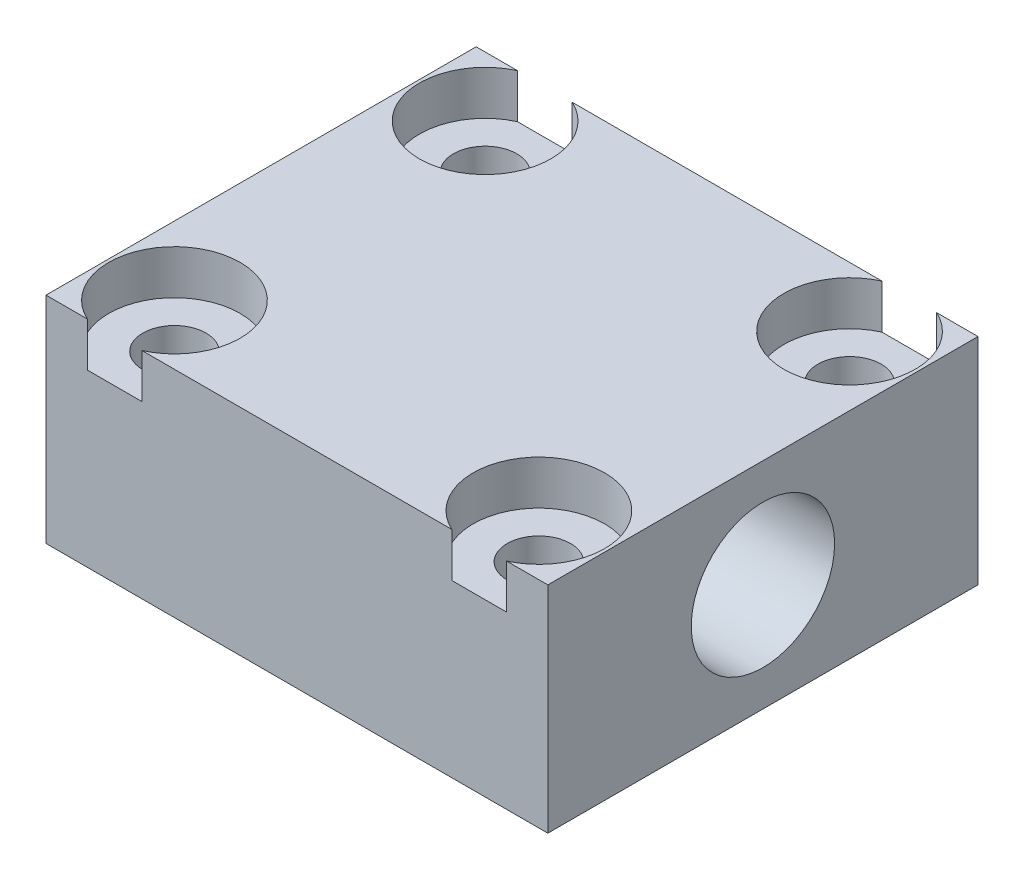
SolidWorks part; units mm, degrees
ref_plane "Front Plane" through (0, 0, 0) normal (0, 0, 1) x (1, 0, 0)
ref_plane "Top Plane" through (0, 0, 0) normal (0, 1, 0) x (1, 0, 0)
ref_plane "Right Plane" through (0, 0, 0) normal (1, 0, 0) x (0, 0, -1)
sketch "Sketch1" plane through (0, 0, 0) normal (0, 1, 0) x (1, 0, 0)
  line L1 (-21, 18) -> (21, 18)
  line L2 (-21, 18) -> (-21, -18)
  line L3 (-21, -18) -> (21, -18)
  line L4 (21, 18) -> (21, -18)
  line L5 (-21, 18) -> (21, -18) construction
  line L6 (-21, -18) -> (21, 18) construction
  point P0 (0, 0)
  dimension "D1" = 36
  dimension "D2" = 42
extrude "Boss-Extrude1" add sketch "Sketch1" along normal blind 18
sketch "Sketch4" plane through (0, 0, 0) normal (0, -1, 0) x (1, 0, 0)
  line L1 (-15.25, -13) -> (15.25, -13) construction
  line L2 (-15.25, -13) -> (-15.25, 13) construction
  line L3 (-15.25, 13) -> (15.25, 13) construction
  line L4 (15.25, -13) -> (15.25, 13) construction
  line L5 (-15.25, -13) -> (15.25, 13) construction
  line L6 (-15.25, 13) -> (15.25, -13) construction
  point P0 (0, 0)
  dimension "D1" = 30.5
  dimension "D2" = 26
hole_wizard "CBORE for M5 Pan Head Machine Screw3" positions "Sketch6" profile "Sketch5" counterbore size "M5" standard "ANSI Metric" end condition through all
sketch "Sketch6" plane through (-6.5491, 18, -3.6896) normal (0, -1, 0) x (-1, 0, 0)
  point P0 (8.7009, -16.6896)
  point P3 (-21.7991, -16.6896)
  point P6 (-21.7991, 9.3104)
  point P9 (8.7009, 9.3104)
sketch "Sketch5" plane through (-15.25, 18, 13) normal (1, 0, 0) x (0, 0, 1)
  line L0 (0, 0) -> (0, 18)
  line L1 (0, 18) -> (2.65, 18)
  line L3 (2.65, 18) -> (2.65, 3.7)
  line L4 (2.65, 3.7) -> (5.5, 3.7)
  line L5 (5.5, 3.7) -> (5.5, 0)
  line L7 (5.5, 0) -> (0, 0)
  line L11 (0, -6.35) -> (0, 107.95) construction
  dimension "Thru Hole Dia." = 5.3
  dimension "Thru Hole Depth" = 18
  dimension "C'Bore Dia." = 11
  dimension "C'Bore Depth" = 3.7
sketch "Sketch7" plane through (21, 0, 0) normal (1, 0, 0) x (0, 0, -1)
  line L0 (0, 18) -> (0, 0) construction
  line L1 (-18, 18) -> (18, 18) construction
  circle A0 centre (0, 9) radius 6
  dimension "D1" = 12
extrude "Cut-Extrude1" cut sketch "Sketch7" against normal through all
